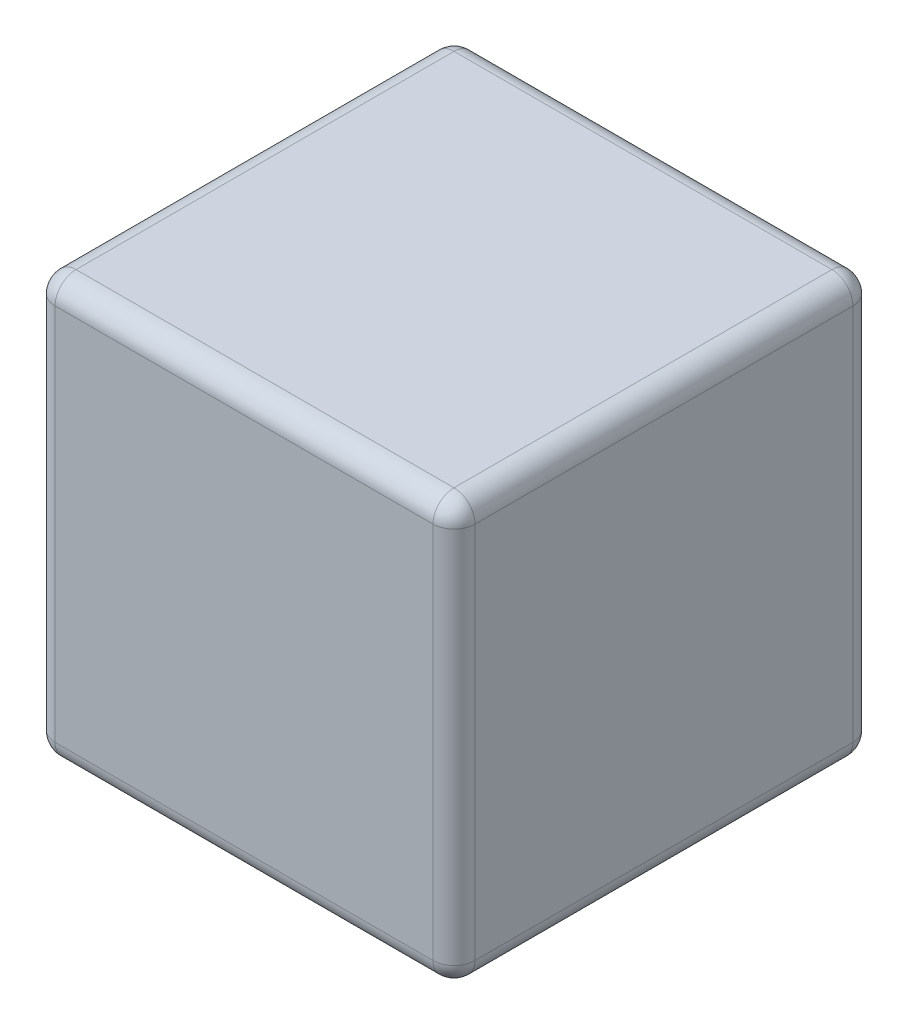
SolidWorks part; units mm, degrees
ref_plane "Front Plane" through (0, 0, 0) normal (0, 0, 1) x (1, 0, 0)
ref_plane "Top Plane" through (0, 0, 0) normal (0, 1, 0) x (1, 0, 0)
ref_plane "Right Plane" through (0, 0, 0) normal (1, 0, 0) x (0, 0, -1)
sketch "Sketch1" plane through (0, 0, 0) normal (0, 1, 0) x (1, 0, 0)
  line L1 (0, 0) -> (20, 0)
  line L2 (0, 0) -> (0, 20)
  line L3 (0, 20) -> (20, 20)
  line L4 (20, 0) -> (20, 20)
  dimension "D1" = 20
  dimension "D2" = 20
extrude "Boss-Extrude1" add sketch "Sketch1" along normal blind 20
fillet "Fillet1" radius 1 12 edges at (20, 10, -20) (20, 0, -10) (10, 0, 0) (0, 10, 0) (20, 10, 0) (20, 20, -10) (10, 20, 0) (0, 0, -10) (10, 0, -20) (0, 10, -20) (0, 20, -10) (10, 20, -20)
